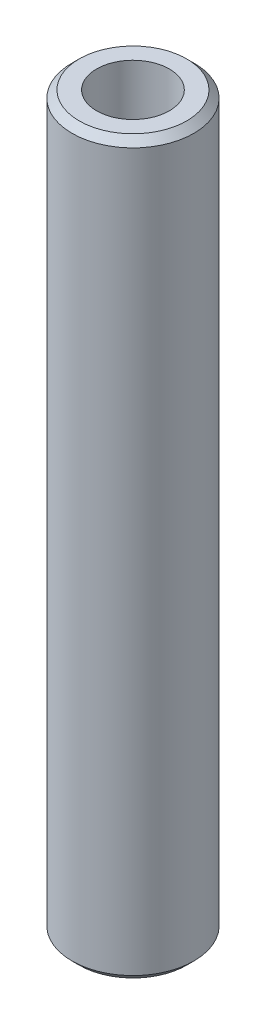
SolidWorks part; units mm, degrees
ref_plane "Front Plane" through (0, 0, 0) normal (0, 0, 1) x (1, 0, 0)
ref_plane "Top Plane" through (0, 0, 0) normal (0, 1, 0) x (1, 0, 0)
ref_plane "Right Plane" through (0, 0, 0) normal (1, 0, 0) x (0, 0, -1)
sketch "Sketch1" plane through (0, 0, 0) normal (0, 1, 0) x (1, 0, 0)
  circle A0 centre (0, 0) radius 50
  dimension "SHAFT_OD" = 100
extrude "Boss-Extrude1" add sketch "Sketch1" along normal blind 600
sketch "Sketch2" plane through (0, 0, 0) normal (0, 1, 0) x (1, 0, 0)
  circle A0 centre (0, 0) radius 29.8254
  dimension "BORE_D" = 59.6507
extrude "Cut-Extrude1" cut sketch "Sketch2" along normal through all
chamfer "Chamfer1" distance 5.8831 angle 45 2 edges at (0, 600, 50) (0, 0, 50)
